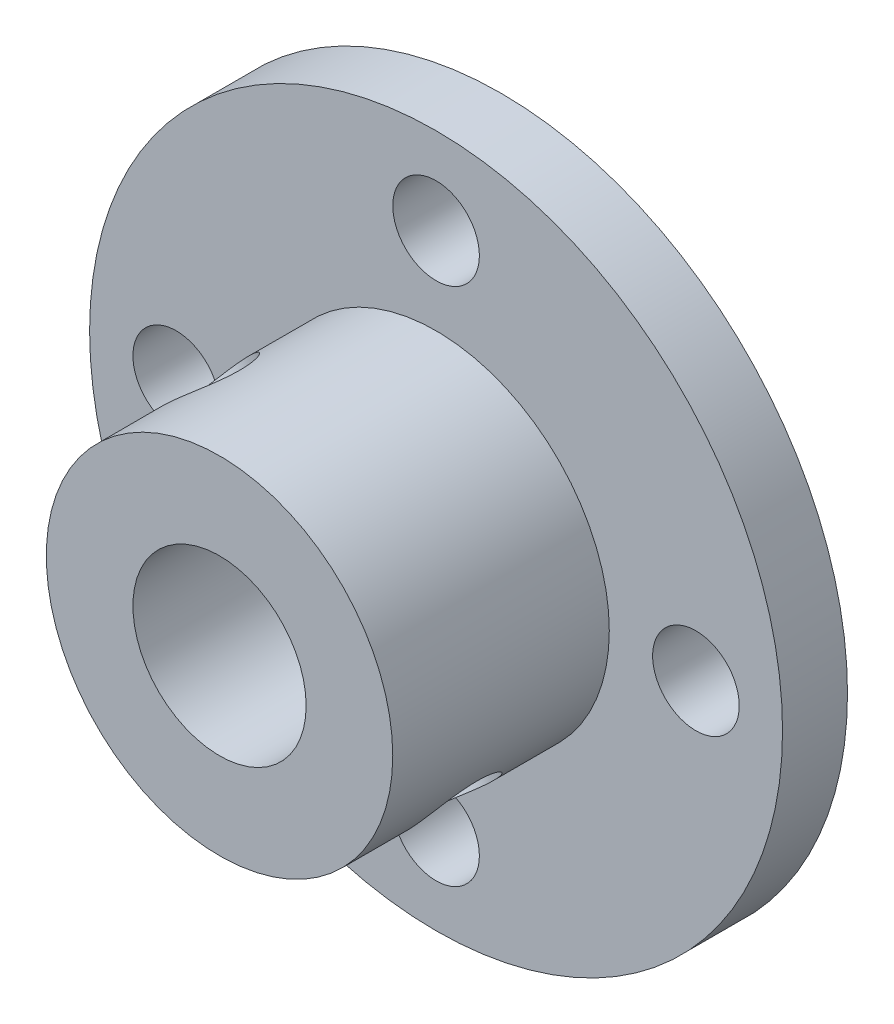
SolidWorks part; units mm, degrees
ref_plane "Front Plane" through (0, 0, 0) normal (0, 0, 1) x (1, 0, 0)
ref_plane "Top Plane" through (0, 0, 0) normal (0, 1, 0) x (1, 0, 0)
ref_plane "Right Plane" through (0, 0, 0) normal (1, 0, 0) x (0, 0, -1)
sketch "Sketch1" plane through (0, 0, 0) normal (0, 0, 1) x (1, 0, 0)
  line L0 (-8.0806, -8.0806) -> (8.0806, 8.0806) construction
  circle A0 centre (0, 0) radius 16
  point P6 (0, 0)
extrude "Boss-Extrude1" add sketch "Sketch1" along normal blind 3
sketch "Sketch2" plane through (0, 0, 3) normal (0, 0, 1) x (1, 0, 0)
  circle A0 centre (0, 0) radius 8
extrude "Boss-Extrude2" add sketch "Sketch2" along normal blind 10
sketch "Sketch3" plane through (0, 0, 13) normal (0, 0, 1) x (1, 0, 0)
  circle A0 centre (0, 0) radius 4
extrude "Cut-Extrude1" cut sketch "Sketch3" against normal up to surface (13 mm away) up to face at (16, 0, 0)
sketch "Sketch4" plane through (0, 0, 3) normal (0, 0, 1) x (1, 0, 0)
  circle A0 centre (0, 0) radius 12 construction
  circle A1 centre (-12, 0) radius 2
  circle A2 centre (0, 12) radius 2
  circle A3 centre (12, 0) radius 2
  circle A4 centre (0, -12) radius 2
  point P14 (0, 0)
  dimension "D1" = 4
extrude "Cut-Extrude2" cut sketch "Sketch4" against normal up to surface (3 mm away) up to face at (4, 0, 0)
ref_axis "Axis1" through (0, 0, 0) along (0, 0, 1)
ref_plane "Plane1" through (0, 0, 0) normal (0.7071, -0.7071, 0) x (0, 0, -1)
sketch "Sketch5" plane through (0, 0, 0) normal (0.7071, -0.7071, 0) x (0, 0, -1)
  line L0 (-13, 0) -> (-3, 0) construction
  line L1 (-13, 8) -> (-13, -8) construction
  line L2 (-3, 8) -> (-3, -8) construction
  circle A0 centre (-8, 0) radius 2
extrude "Cut-Extrude3" cut sketch "Sketch5" against normal up to surface and the other way up to surface up to face at (8, 0, 13) other way up to face at (8, 0, 13)
